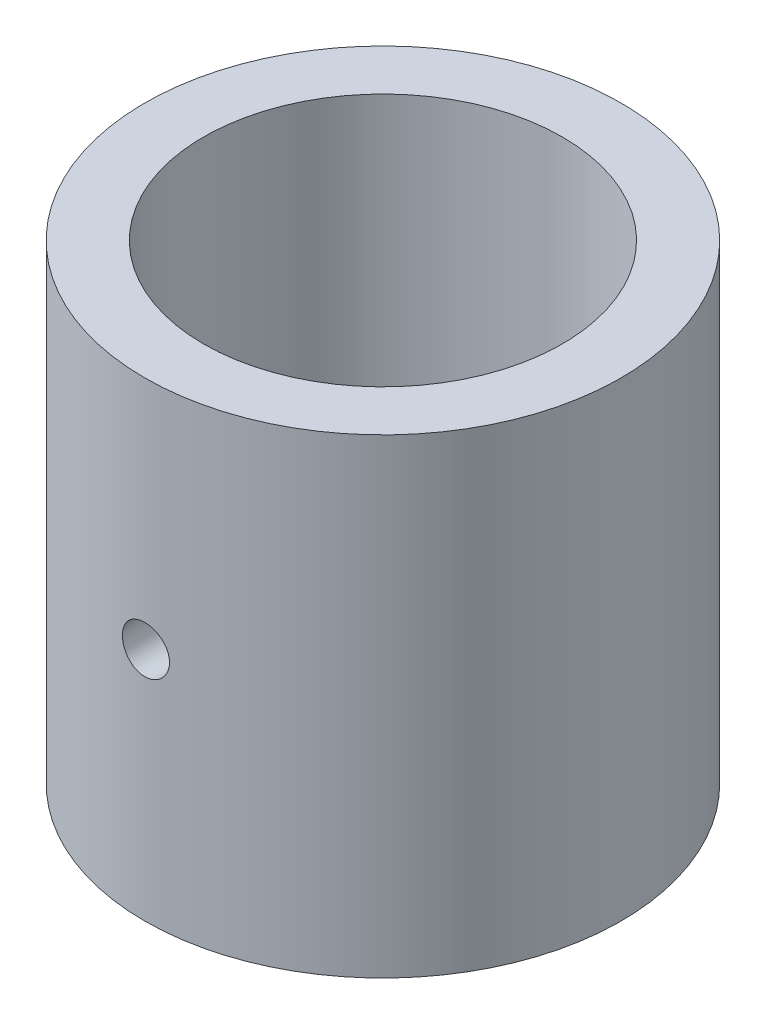
SolidWorks part; units mm, degrees
ref_plane "Front Plane" through (0, 0, 0) normal (0, 0, 1) x (1, 0, 0)
ref_plane "Top Plane" through (0, 0, 0) normal (0, 1, 0) x (1, 0, 0)
ref_plane "Right Plane" through (0, 0, 0) normal (1, 0, 0) x (0, 0, -1)
sketch "Sketch1" plane through (0, 0, 0) normal (0, 1, 0) x (1, 0, 0)
  circle A0 centre (0, 0) radius 15.25
  circle A1 centre (0, 0) radius 20.25
  dimension "D1" = 30.5
  dimension "D2" = 5
extrude "Boss-Extrude1" add sketch "Sketch1" along normal blind 40
ref_plane "Plane1" through (0, 0, 20.25) normal (0, 0, 1) x (1, 0, 0)
sketch "Sketch2" plane through (0, 0, 20.25) normal (0, 0, 1) x (1, 0, 0)
  line L0 (-20.25, 0) -> (20.25, 0) construction
  circle A0 centre (0, 20) radius 2
  point P0 (0, 20)
  dimension "D2" = 4
  dimension "D1" = 20
extrude "Cut-Extrude1" cut sketch "Sketch2" against normal blind 42
